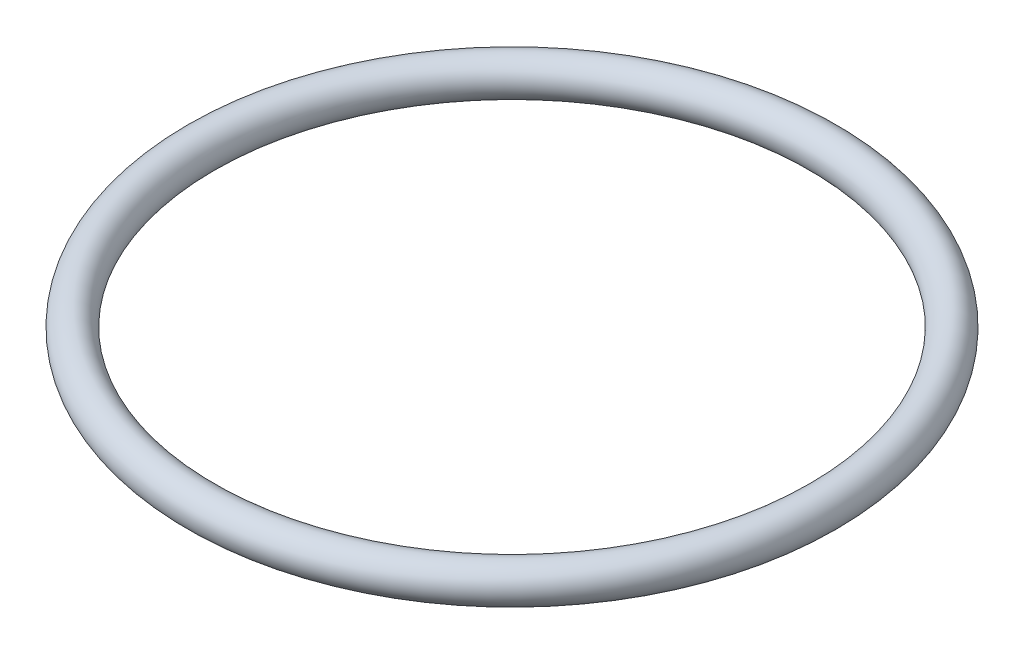
SolidWorks part; units mm, degrees
ref_plane "Plano frontal" through (0, 0, 0) normal (0, 0, 1) x (1, 0, 0)
ref_plane "Plano superior" through (0, 0, 0) normal (0, 1, 0) x (1, 0, 0)
ref_plane "Plano direito" through (0, 0, 0) normal (1, 0, 0) x (0, 0, -1)
sketch "Esboço1" plane through (0, 0, 0) normal (0, 1, 0) x (1, 0, 0)
  line L1 (0, 49.7625) -> (0, -49.7625) construction
  line L2 (-49.7625, 0) -> (49.7625, 0) construction
  circle A0 centre (0, 0) radius 45 construction
  circle A1 centre (0, 0) radius 49.7625 construction
  circle A2 centre (0, 0) radius 52.9375
  dimension "D1" = 90
  dimension "D2" = 4.7625
  dimension "D3" = 3.175
sketch "Esboço3" plane through (0, 0, 0) normal (0, 0, 1) x (1, 0, 0)
  circle A0 centre (-52.9375, 0) radius 3.175
  point P4 (-45, 0)
sweep "Varredura1" add profiles "Esboço3" path "Esboço1"
ref_axis "Eixo1" through (0, 0, 0) along (0, 1, 0)
ref_plane "Plano1" through (0, 0, 0) normal (0, 1, 0) x (1, 0, 0)
